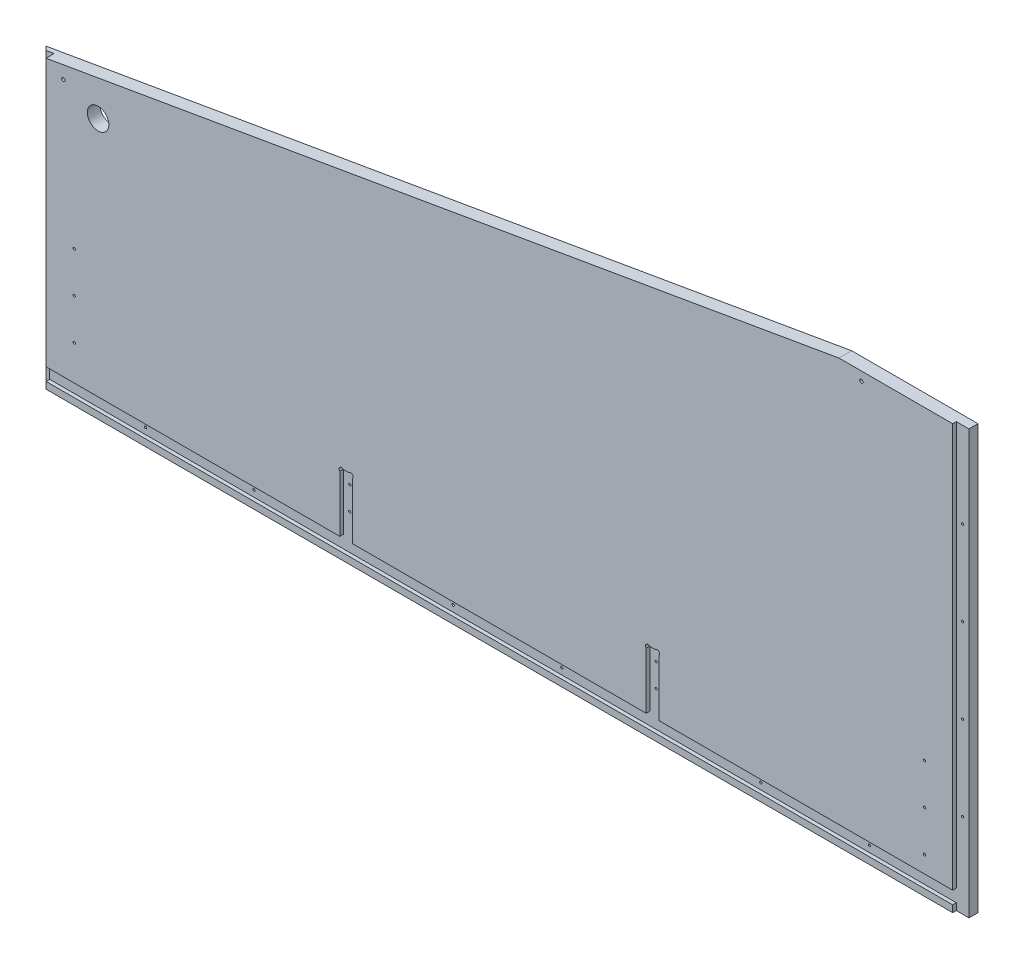
SolidWorks part; units mm, degrees
material "Maple"
ref_plane "Front Plane" through (0, 0, 0) normal (0, 0, 1) x (1, 0, 0)
ref_plane "Top Plane" through (0, 0, 0) normal (0, 1, 0) x (1, 0, 0)
ref_plane "Right Plane" through (0, 0, 0) normal (1, 0, 0) x (0, 0, -1)
sketch "Sketch1" plane through (0, 0, 0) normal (0, 0, 1) x (1, 0, 0)
  line L0 (8932.6508, -5243.5125) -> (10226.1458, -5243.5125)
  line L1 (9086.3208, -4722.0918) -> (10222.9708, -4853.7812)
  line L2 (8914.8708, -6342.0625) -> (10197.5708, -6342.0625)
  line L3 (8914.8708, -5808.6625) -> (10197.5708, -5808.6625)
  line L4 (8919.6333, -5253.0375) -> (10218.2083, -5253.0375)
  line L5 (9134.2633, -4656.1375) -> (9134.2633, -4638.3575)
  line L6 (9091.0833, -4638.3575) -> (9134.2633, -4638.3575)
  line L7 (9091.0833, -4567.2375) -> (9091.0833, -4638.3575)
  line L8 (9134.2633, -4656.1375) -> (9581.3033, -4656.1375)
  line L9 (9091.0833, -4567.2375) -> (9624.4833, -4567.2375)
  line L10 (9581.3033, -4656.1375) -> (9581.3033, -4638.3575)
  line L11 (9581.3033, -4638.3575) -> (9624.4833, -4638.3575)
  line L12 (9624.4833, -4567.2375) -> (9624.4833, -4638.3575)
  line L13 (8932.6508, -5225.7325) -> (9344.9775, -5225.7325)
  line L14 (8932.6508, -5256.2125) -> (8932.6508, -5243.5125)
  line L15 (8911.6958, -5256.2125) -> (8932.6508, -5256.2125)
  line L16 (8914.8708, -4722.0918) -> (9086.3208, -4722.0918)
  line L17 (8911.6958, -4715.5913) -> (8932.6508, -4715.5913)
  line L18 (8914.8708, -6342.0625) -> (8914.8708, -5808.6625)
  line L19 (12082.9917, -4722.0918) -> (10946.3417, -4853.7812)
  line L20 (12236.6617, -5243.5125) -> (10943.1667, -5243.5125)
  line L21 (10951.1042, -5253.0375) -> (12249.6792, -5253.0375)
  line L22 (10838.3917, -5656.2625) -> (11308.2917, -5656.2625)
  line L23 (10838.3917, -5719.7625) -> (11308.2917, -5719.7625)
  line L24 (10838.3917, -5742.5368) -> (11308.2917, -5742.5368)
  line L25 (10806.6417, -6342.0625) -> (11340.0417, -6342.0625)
  line L26 (10803.4667, -6335.7125) -> (11343.2167, -6335.7125)
  line L27 (10803.4667, -6317.9325) -> (11343.2167, -6317.9325)
  line L28 (10943.1667, -5225.7325) -> (11376.4483, -5225.7325)
  line L29 (11506.7292, -4754.5625) -> (10806.6417, -4827.5875)
  line L30 (11506.7292, -4567.2375) -> (11506.7292, -4754.5625)
  line L31 (10806.6417, -4567.2375) -> (10806.6417, -4827.5875)
  line L32 (10806.6417, -4567.2375) -> (11506.7292, -4567.2375)
  line L33 (10235.6708, -6329.3625) -> (10245.1958, -6329.3625)
  line L34 (10245.1958, -6329.3625) -> (10254.7208, -6278.5625)
  line L35 (10302.3458, -6329.3625) -> (10311.8708, -6278.5625)
  line L36 (10302.3458, -6329.3625) -> (10292.8208, -6329.3625)
  line L37 (10245.1958, -5821.3625) -> (10254.7208, -5872.1625)
  line L38 (10235.6708, -5821.3625) -> (10245.1958, -5821.3625)
  line L39 (10292.8208, -5821.3625) -> (10302.3458, -5821.3625)
  line L40 (10302.3458, -5821.3625) -> (10311.8708, -5872.1625)
  line L41 (10235.6708, -5821.3625) -> (10235.6708, -6329.3625)
  line L42 (10254.7208, -5872.1625) -> (10254.7208, -6278.5625)
  line L43 (10311.8708, -5872.1625) -> (10311.8708, -6278.5625)
  line L44 (10292.8208, -5821.3625) -> (10292.8208, -6329.3625)
  line L45 (8932.6508, -5225.7325) -> (8932.6508, -4715.5913)
  line L46 (8911.6958, -4715.5913) -> (8911.6958, -5256.2125)
  line L47 (8914.8708, -5248.275) -> (8914.8708, -4722.0918)
  line L48 (8919.6333, -5253.0375) -> (8914.8708, -5248.275)
  line L49 (8914.8708, -5145.0875) -> (8937.426, -5145.0875)
  line L50 (8914.8708, -5202.2375) -> (8937.426, -5202.2375)
  line L51 (10838.3917, -5656.2625) -> (10838.3917, -5719.7625)
  line L52 (10832.0417, -5736.1868) -> (10856.1717, -5736.1868)
  line L53 (10806.6417, -6342.0625) -> (10806.6417, -5818.7368)
  line L54 (10832.0417, -5649.9125) -> (10856.1717, -5649.9125)
  line L55 (10832.0417, -5726.1125) -> (10856.1717, -5726.1125)
  line L56 (10806.6417, -5818.7368) -> (10833.9015, -5818.7368)
  line L57 (10832.0417, -5806.0442) -> (10851.6815, -5806.0442)
  line L58 (10856.1717, -5801.5541) -> (10856.1717, -5736.1868)
  line L59 (10838.3917, -5814.2467) -> (10838.3917, -5742.5368)
  line L60 (10832.0417, -5806.0442) -> (10832.0417, -5736.1868)
  line L61 (10803.4667, -6317.9325) -> (10803.4667, -6335.7125)
  line L62 (10197.5708, -5808.6625) -> (10197.5708, -6342.0625)
  line L63 (9762.3842, -6348.4125) -> (9762.3842, -5802.3125)
  line L64 (9780.1642, -6348.4125) -> (9762.3842, -6348.4125)
  line L65 (9780.1642, -5802.3125) -> (9780.1642, -6348.4125)
  line L66 (9762.3842, -5802.3125) -> (9780.1642, -5802.3125)
  line L67 (9332.2775, -6348.4125) -> (9332.2775, -5802.3125)
  line L68 (9332.2775, -6348.4125) -> (9350.0575, -6348.4125)
  line L69 (9350.0575, -5802.3125) -> (9350.0575, -6348.4125)
  line L70 (9332.2775, -5802.3125) -> (9350.0575, -5802.3125)
  line L71 (9993.8374, -6061.075) -> (9993.8374, -6045.2418)
  line L72 (9998.5999, -6065.8375) -> (10014.4331, -6065.8375)
  line L73 (9998.5999, -6084.8875) -> (10014.4331, -6084.8875)
  line L74 (9993.8374, -6105.4832) -> (9993.8374, -6089.65)
  line L75 (9974.7874, -6105.4832) -> (9974.7874, -6089.65)
  line L76 (9954.1917, -6084.8875) -> (9970.0249, -6084.8875)
  line L77 (9974.7874, -6061.075) -> (9974.7874, -6045.2418)
  line L78 (9954.1917, -6065.8375) -> (9970.0249, -6065.8375)
  line L79 (10793.9417, -6237.2875) -> (10816.4969, -6237.2875)
  line L80 (10793.9417, -6294.4375) -> (10816.4969, -6294.4375)
  line L81 (10856.1717, -5649.9125) -> (10856.1717, -5726.1125)
  line L82 (10832.0417, -5726.1125) -> (10832.0417, -5649.9125)
  line L83 (10226.1458, -5225.7325) -> (10226.1458, -5243.5125)
  line L84 (10205.1908, -5257.8) -> (10205.1908, -4844.2499)
  line L85 (10230.9083, -4844.2499) -> (10230.9083, -5257.8)
  line L86 (10205.1908, -5257.8) -> (10230.9083, -5257.8)
  line L87 (10205.1908, -4844.2499) -> (10230.9083, -4844.2499)
  line L88 (10946.3417, -5176.8375) -> (10968.8969, -5176.8375)
  line L89 (9349.4676, -5141.9125) -> (9358.2674, -5141.9125)
  line L90 (10946.3417, -5119.6875) -> (10968.8969, -5119.6875)
  line L91 (9929.011, -4660.9635) -> (10066.0807, -4660.9635)
  line L92 (9929.011, -4678.7435) -> (10066.0807, -4678.7435)
  line L93 (10943.1667, -5225.7325) -> (10943.1667, -5243.5125)
  line L94 (10946.3417, -5248.275) -> (10951.1042, -5253.0375)
  line L95 (10946.3417, -5257.8063) -> (10946.3417, -4849.0188)
  line L96 (10964.1217, -5257.8) -> (10964.1217, -4844.2499)
  line L97 (10938.4042, -4844.2499) -> (10938.4042, -5257.8)
  line L98 (10938.4042, -5257.8) -> (10964.1217, -5257.8)
  line L99 (10964.1217, -4844.2499) -> (10938.4042, -4844.2499)
  line L100 (10344.8908, -4560.8875) -> (10369.0208, -4560.8875)
  line L101 (10344.8908, -4560.8875) -> (10369.0208, -4560.8875)
  line L102 (10800.2917, -4560.8875) -> (10824.4217, -4560.8875)
  line L103 (10200.4156, -5119.6875) -> (10222.9708, -5119.6875)
  line L104 (10200.4156, -5176.8375) -> (10222.9708, -5176.8375)
  line L105 (9344.9775, -5146.4026) -> (9344.9775, -5225.7325)
  line L106 (10344.8908, -4560.8875) -> (10344.8908, -4833.9375)
  line L107 (9792.8642, -5225.7325) -> (9792.8642, -5146.4026)
  line L108 (9362.7575, -5225.7325) -> (9775.0842, -5225.7325)
  line L109 (9680.3633, -4761.8396) -> (9680.3633, -4559.9604)
  line L110 (9656.2333, -4559.9604) -> (9680.3633, -4559.9604)
  line L111 (9656.2333, -4761.8396) -> (9680.3633, -4761.8396)
  line L112 (9656.2333, -4761.8396) -> (9656.2333, -4559.9604)
  line L113 (9779.5743, -5141.9125) -> (9788.374, -5141.9125)
  line L114 (10070.5708, -4665.4536) -> (10070.5708, -4674.2534)
  line L115 (9924.5208, -4674.2534) -> (9924.5208, -4665.4536)
  line L116 (12127.4417, -6188.3925) -> (12205.5015, -6188.3925)
  line L117 (12209.9917, -6170.6125) -> (12209.9917, -6183.9024)
  line L118 (9792.8642, -5225.7325) -> (10226.1458, -5225.7325)
  line L119 (9662.5833, -4754.5625) -> (10362.6708, -4827.5875)
  line L120 (9662.5833, -4567.2375) -> (9662.5833, -4754.5625)
  line L121 (10362.6708, -4567.2375) -> (10362.6708, -4827.5875)
  line L122 (9662.5833, -4567.2375) -> (10362.6708, -4567.2375)
  line L123 (10824.4217, -4833.9375) -> (10800.2917, -4833.9375)
  line L124 (10800.2917, -4833.9375) -> (10800.2917, -4560.8875)
  line L125 (10824.4217, -4560.8875) -> (10824.4217, -4833.9375)
  line L126 (10344.8908, -4833.9375) -> (10369.0208, -4833.9375)
  line L127 (10369.0208, -4833.9375) -> (10369.0208, -4560.8875)
  line L128 (10222.9708, -5248.275) -> (10218.2083, -5253.0375)
  line L129 (10222.9708, -5257.8063) -> (10222.9708, -4849.0188)
  line L130 (11734.6544, -5701.375) -> (11739.2301, -5701.375)
  line L131 (9362.7575, -5225.7325) -> (9362.7575, -5146.4026)
  line L132 (9775.0842, -5146.4026) -> (9775.0842, -5225.7325)
  line L133 (11761.3864, -5701.375) -> (11756.8282, -5701.375)
  line L134 (11734.6544, -5693.755) -> (11739.2301, -5693.755)
  line L135 (11761.4039, -5693.755) -> (11756.8282, -5693.755)
  line L136 (11734.6544, -5701.375) -> (11739.2301, -5701.375)
  line L137 (11744.3462, -5721.3024) -> (11744.3462, -5706.4179)
  line L138 (11751.7122, -5721.3024) -> (11751.7122, -5706.4179)
  line L139 (11740.0917, -6170.6125) -> (11740.0917, -6183.9024)
  line L140 (11689.2917, -6188.3925) -> (11822.6417, -6188.3925)
  line L141 (11689.2917, -6348.4093) -> (11689.2917, -6164.2657)
  line L142 (11689.2917, -6164.2657) -> (11746.4417, -6164.2657)
  line L143 (11746.4417, -6164.2657) -> (11746.4417, -6188.3925)
  line L144 (11689.2917, -6164.2657) -> (11746.4417, -6164.2657)
  line L145 (11340.0417, -5818.7368) -> (11340.0417, -6342.0625)
  line L146 (11290.5117, -5726.1125) -> (11314.6417, -5726.1125)
  line L147 (11290.5117, -5649.9125) -> (11290.5117, -5726.1125)
  line L148 (11340.0417, -5818.7368) -> (11312.7818, -5818.7368)
  line L149 (11314.6417, -5806.0442) -> (11295.0018, -5806.0442)
  line L150 (11290.5117, -5801.5541) -> (11290.5117, -5736.1868)
  line L151 (11308.2917, -5814.2467) -> (11308.2917, -5742.5368)
  line L152 (11314.6417, -5806.0442) -> (11314.6417, -5736.1868)
  line L153 (11290.5117, -5736.1868) -> (11314.6417, -5736.1868)
  line L154 (11848.0417, -6267.1325) -> (11962.3417, -6267.1325)
  line L155 (11962.3417, -6267.1325) -> (11962.3417, -6203.6325)
  line L156 (11343.2167, -6317.9325) -> (11343.2167, -6335.7125)
  line L157 (11365.4417, -5656.2625) -> (11365.4417, -5719.7625)
  line L158 (11365.4417, -5656.2625) -> (11479.7417, -5656.2625)
  line L159 (11778.1917, -6071.3937) -> (11802.3217, -6071.3937)
  line L160 (11314.6417, -5726.1125) -> (11314.6417, -5649.9125)
  line L161 (11314.6417, -5649.9125) -> (11290.5117, -5649.9125)
  line L162 (11308.2917, -5719.7625) -> (11308.2917, -5656.2625)
  line L163 (11689.2917, -6348.4093) -> (11713.4217, -6348.4093)
  line L164 (12203.6417, -6164.2657) -> (12260.7917, -6164.2657)
  line L165 (11713.4217, -6348.4093) -> (11713.4217, -6164.2657)
  line L166 (11695.6417, -6342.0625) -> (11695.6417, -6170.6125)
  line L167 (11695.6417, -6048.5337) -> (11699.4517, -6052.3437)
  line L168 (11822.6417, -6292.5325) -> (11822.6417, -6188.3925)
  line L169 (11695.6417, -6342.0625) -> (11695.6417, -6170.6125)
  line L170 (11848.0417, -6203.6325) -> (11962.3417, -6203.6325)
  line L171 (11848.0417, -6203.6325) -> (11848.0417, -6267.1325)
  line L172 (11987.7417, -6267.1325) -> (11987.7417, -6203.6325)
  line L173 (11784.5417, -6077.7437) -> (11784.5417, -6141.2438)
  line L174 (11517.8417, -5656.2625) -> (11632.1417, -5656.2625)
  line L175 (11632.1417, -5656.2625) -> (11632.1417, -5719.7625)
  line L176 (11632.1417, -5719.7625) -> (11517.8417, -5719.7625)
  line L177 (11517.8417, -5719.7625) -> (11517.8417, -5656.2625)
  line L178 (11692.4667, -6028.2137) -> (11692.4667, -6045.9937)
  line L179 (11695.6417, -5979.3188) -> (11718.1969, -5979.3188)
  line L180 (11695.6417, -5922.1687) -> (11718.1969, -5922.1687)
  line L181 (11821.0415, -5722.9375) -> (11821.0415, -5943.6)
  line L182 (11687.7042, -5651.5) -> (11701.9917, -5651.5)
  line L183 (11687.7042, -5651.5) -> (11687.7042, -6055.5251)
  line L184 (11687.7042, -6055.5251) -> (11701.9917, -6055.5251)
  line L185 (11701.9917, -6055.5251) -> (11701.9917, -5651.5)
  line L186 (11695.6417, -6055.2013) -> (11695.6417, -5649.595)
  line L187 (11695.6417, -5656.2625) -> (11695.6417, -6048.5337)
  line L188 (11695.6417, -6170.6125) -> (11740.0917, -6170.6125)
  line L189 (12203.6417, -6164.2657) -> (12203.6417, -6188.3925)
  line L190 (12254.4417, -6342.0625) -> (12254.4417, -6170.6125)
  line L191 (12129.0419, -5943.6) -> (12129.0419, -5722.9375)
  line L192 (12254.4417, -6048.5337) -> (12250.6317, -6052.3437)
  line L193 (12257.6167, -6045.9937) -> (12257.6167, -6028.2137)
  line L194 (12248.0917, -5651.5) -> (12262.3792, -5651.5)
  line L195 (12262.3792, -5651.5) -> (12262.3792, -6055.5251)
  line L196 (12262.3792, -6055.5251) -> (12248.0917, -6055.5251)
  line L197 (12248.0917, -6055.5251) -> (12248.0917, -5651.5)
  line L198 (12254.4417, -6141.2438) -> (12254.4417, -6077.7437)
  line L199 (12236.6617, -6164.2657) -> (12260.7917, -6164.2657)
  line L200 (12102.0417, -6267.1325) -> (11987.7417, -6267.1325)
  line L201 (11330.1865, -6237.2875) -> (11352.7417, -6237.2875)
  line L202 (11330.1865, -6294.4375) -> (11352.7417, -6294.4375)
  line L203 (11474.6617, -5851.8425) -> (11492.4417, -5851.8425)
  line L204 (11474.6617, -5808.6625) -> (11474.6617, -5851.8425)
  line L205 (11403.5417, -5808.6625) -> (11474.6617, -5808.6625)
  line L206 (11492.4417, -5851.8425) -> (11492.4417, -6298.8825)
  line L207 (11403.5417, -6342.0625) -> (11403.5417, -5808.6625)
  line L208 (11474.6617, -6298.8825) -> (11492.4417, -6298.8825)
  line L209 (11474.6617, -6342.0625) -> (11474.6617, -6298.8825)
  line L210 (11403.5417, -6342.0625) -> (11474.6617, -6342.0625)
  line L211 (11619.4417, -5851.8425) -> (11601.6617, -5851.8425)
  line L212 (11601.6617, -5808.6625) -> (11601.6617, -5851.8425)
  line L213 (11530.5417, -5808.6625) -> (11601.6617, -5808.6625)
  line L214 (11619.4417, -5851.8425) -> (11619.4417, -6298.8825)
  line L215 (11530.5417, -6342.0625) -> (11530.5417, -5808.6625)
  line L216 (11619.4417, -6298.8825) -> (11601.6617, -6298.8825)
  line L217 (11601.6617, -6342.0625) -> (11601.6617, -6298.8825)
  line L218 (11530.5417, -6342.0625) -> (11601.6617, -6342.0625)
  line L219 (11479.7417, -5719.7625) -> (11479.7417, -5656.2625)
  line L220 (11365.4417, -5719.7625) -> (11479.7417, -5719.7625)
  line L221 (11778.1917, -6147.5937) -> (11802.3217, -6147.5937)
  line L222 (11802.3217, -6071.3937) -> (11802.3217, -6147.5937)
  line L223 (11778.1917, -6147.5937) -> (11778.1917, -6071.3937)
  line L224 (12254.4417, -5922.1687) -> (12231.8865, -5922.1687)
  line L225 (12254.4417, -5979.3188) -> (12231.8865, -5979.3188)
  line L226 (12254.4417, -6055.2013) -> (12254.4417, -5649.595)
  line L227 (12254.4417, -6048.5337) -> (12254.4417, -5656.2625)
  line L228 (11841.6917, -5702.2873) -> (12108.3917, -5702.2873)
  line L229 (11822.6417, -6292.5325) -> (12127.4417, -6292.5325)
  line L230 (12127.4417, -6292.5325) -> (12127.4417, -6188.3925)
  line L231 (12254.4417, -6170.6125) -> (12209.9917, -6170.6125)
  line L232 (11695.6417, -6342.0625) -> (12254.4417, -6342.0625)
  line L233 (12236.6617, -6348.4093) -> (12260.7917, -6348.4093)
  line L234 (12260.7917, -6348.4093) -> (12260.7917, -6164.2657)
  line L235 (12236.6617, -6348.4093) -> (12236.6617, -6164.2657)
  line L236 (12102.0417, -6203.6325) -> (12102.0417, -6267.1325)
  line L237 (11987.7417, -6203.6325) -> (12102.0417, -6203.6325)
  line L238 (12236.6617, -6147.5937) -> (12236.6617, -6071.3937)
  line L239 (12203.6417, -6188.3925) -> (12260.7917, -6188.3925)
  line L240 (11098.7417, -4665.4536) -> (11098.7417, -4674.2534)
  line L241 (11394.2283, -5146.4026) -> (11394.2283, -5225.7325)
  line L242 (11376.4483, -5225.7325) -> (11376.4483, -5146.4026)
  line L243 (11394.2283, -5225.7325) -> (11806.555, -5225.7325)
  line L244 (11841.6917, -5964.2502) -> (12108.3917, -5964.2502)
  line L245 (12236.6617, -6147.5937) -> (12260.7917, -6147.5937)
  line L246 (12236.6617, -5256.2125) -> (12236.6617, -5243.5125)
  line L247 (12260.7917, -6147.5937) -> (12260.7917, -6071.3937)
  line L248 (12260.7917, -6071.3937) -> (12236.6617, -6071.3937)
  line L249 (12254.4417, -6077.7437) -> (11784.5417, -6077.7437)
  line L250 (11784.5417, -6141.2438) -> (12254.4417, -6141.2438)
  line L252 (12254.4417, -5656.2625) -> (11695.6417, -5656.2625)
  line L253 (11699.4517, -6052.3437) -> (12250.6317, -6052.3437)
  line L254 (11692.4667, -6045.9937) -> (12257.6167, -6045.9937)
  line L255 (11692.4667, -6028.2137) -> (12257.6167, -6028.2137)
  line L256 (11824.335, -5146.4026) -> (11824.335, -5225.7325)
  line L257 (11811.0451, -5141.9125) -> (11819.8449, -5141.9125)
  line L258 (11244.7917, -4674.2534) -> (11244.7917, -4665.4536)
  line L259 (11806.555, -5225.7325) -> (11806.555, -5146.4026)
  line L260 (11488.9492, -4761.8396) -> (11488.9492, -4559.9604)
  line L261 (11488.9492, -4559.9604) -> (11513.0792, -4559.9604)
  line L262 (11488.9492, -4761.8396) -> (11513.0792, -4761.8396)
  line L263 (11513.0792, -4761.8396) -> (11513.0792, -4559.9604)
  line L264 (11240.3015, -4660.9635) -> (11103.2318, -4660.9635)
  line L265 (11103.2318, -4678.7435) -> (11240.3015, -4678.7435)
  line L266 (12236.6617, -5225.7325) -> (12236.6617, -4715.5913)
  line L267 (12257.6167, -4715.5913) -> (12257.6167, -5256.2125)
  line L268 (12254.4417, -5248.275) -> (12254.4417, -4722.0918)
  line L269 (12236.6617, -5225.7325) -> (11824.335, -5225.7325)
  line L270 (12035.0492, -4656.1375) -> (12035.0492, -4638.3575)
  line L271 (12078.2292, -4638.3575) -> (12035.0492, -4638.3575)
  line L272 (12078.2292, -4567.2375) -> (12078.2292, -4638.3575)
  line L273 (12035.0492, -4656.1375) -> (11588.0092, -4656.1375)
  line L274 (11544.8292, -4567.2375) -> (12078.2292, -4567.2375)
  line L275 (11588.0092, -4656.1375) -> (11588.0092, -4638.3575)
  line L276 (11544.8292, -4638.3575) -> (11588.0092, -4638.3575)
  line L277 (11544.8292, -4567.2375) -> (11544.8292, -4638.3575)
  line L278 (12249.6792, -5253.0375) -> (12254.4417, -5248.275)
  line L280 (12257.6167, -5256.2125) -> (12236.6617, -5256.2125)
  line L281 (12231.8865, -5145.0875) -> (12254.4417, -5145.0875)
  line L282 (12231.8865, -5202.2375) -> (12254.4417, -5202.2375)
  line L283 (12236.6617, -4715.5913) -> (12257.6167, -4715.5913)
  line L284 (12082.9917, -4722.0918) -> (12254.4417, -4722.0918)
  line L285 (11380.9385, -5141.9125) -> (11389.7382, -5141.9125)
  circle A0 centre (8923.7608, -4778.9042) radius 1.5875
  circle A1 centre (9062.6598, -4736.3765) radius 2.3685
  circle A2 centre (9051.3958, -6281.7375) radius 22.225
  circle A3 centre (9083.1458, -6249.9875) radius 1.5875
  circle A4 centre (9083.1458, -6313.4875) radius 1.5875
  circle A5 centre (9019.6458, -6249.9875) radius 1.5875
  circle A6 centre (9019.6458, -6313.4875) radius 1.5875
  circle A7 centre (8972.3383, -5202.2375) radius 1.5875
  circle A8 centre (8923.7608, -5015.9708) radius 1.5875
  circle A9 centre (8923.7608, -5134.5042) radius 1.5875
  circle A10 centre (9054.5708, -5234.6225) radius 1.5875
  circle A11 centre (8923.7608, -4897.4375) radius 1.5875
  circle A12 centre (8972.3383, -5087.9375) radius 1.5875
  circle A13 centre (8972.3383, -5145.0875) radius 1.5875
  circle A14 centre (10847.2817, -5668.9625) radius 1.5875
  circle A15 centre (10847.2817, -5707.0625) radius 1.5875
  circle A16 centre (10847.2817, -5755.2368) radius 1.5875
  circle A17 centre (10851.4092, -6237.2875) radius 1.5875
  circle A18 centre (10851.4092, -6294.4375) radius 1.5875
  circle A19 centre (10847.2817, -5793.3442) radius 1.5875
  arc A20 (10833.9015, -5818.7368) -> (10838.3917, -5814.2467) centre (10836.1466, -5816.4918) ccw
  arc A21 (10851.6815, -5806.0442) -> (10856.1717, -5801.5541) centre (10853.9266, -5803.7992) ccw
  circle A22 centre (10882.8417, -6040.4375) radius 1.5875
  circle A23 centre (10882.8417, -6218.2375) radius 1.5875
  circle A24 centre (10882.8417, -5862.6375) radius 1.5875
  circle A25 centre (10908.2417, -6326.8225) radius 1.5875
  circle A26 centre (10908.2417, -6326.8225) radius 1.5875
  circle A27 centre (10851.4092, -6180.1375) radius 1.5875
  circle A28 centre (10815.5317, -4783.4231) radius 1.5875
  circle A29 centre (10815.5317, -4696.9488) radius 1.5875
  circle A30 centre (10815.5317, -4610.4746) radius 1.5875
  circle A31 centre (10979.1323, -4867.0082) radius 2.3685
  circle A32 centre (10190.1802, -4867.0082) radius 2.3685
  circle A33 centre (10955.2317, -4929.9812) radius 1.5875
  circle A34 centre (10955.2317, -5031.5812) radius 1.5875
  circle A35 centre (10214.0808, -4929.9812) radius 1.5875
  circle A36 centre (10214.0808, -5031.5812) radius 1.5875
  circle A37 centre (9341.1675, -6265.8625) radius 1.5875
  circle A38 centre (9771.2742, -5884.8625) radius 1.5875
  circle A39 centre (9771.2742, -6138.8625) radius 1.5875
  circle A40 centre (9771.2742, -6011.8625) radius 1.5875
  arc A41 (10036.2287, -6113.8083) -> (10051.3426, -6111.6033) centre (10042.9639, -6107.0732) ccw
  arc A42 (10051.3426, -6111.6033) -> (10051.3426, -6039.1217) centre (9984.3124, -6075.3625) ccw
  arc A43 (10051.3426, -6039.1217) -> (10036.2287, -6036.9167) centre (10042.9639, -6043.6518) ccw
  arc A44 (10034.5851, -6102.5431) -> (10034.5851, -6048.1819) centre (9984.3124, -6075.3625) ccw
  arc A45 (10034.5851, -6102.5431) -> (10036.2287, -6113.8083) centre (10042.9639, -6107.0732) ccw
  arc A46 (10036.2287, -6036.9167) -> (10034.5851, -6048.1819) centre (10042.9639, -6043.6518) ccw
  arc A47 (9945.8666, -6127.2787) -> (9948.0717, -6142.3927) centre (9952.6018, -6134.0139) ccw
  arc A48 (9948.0717, -6142.3927) -> (10020.5532, -6142.3927) centre (9984.3124, -6075.3625) ccw
  arc A49 (10020.5532, -6142.3927) -> (10022.7583, -6127.2787) centre (10016.0231, -6134.0139) ccw
  arc A50 (9957.1319, -6125.6352) -> (10011.493, -6125.6352) centre (9984.3124, -6075.3625) ccw
  arc A51 (9957.1319, -6125.6352) -> (9945.8666, -6127.2787) centre (9952.6018, -6134.0139) ccw
  arc A52 (10022.7583, -6127.2787) -> (10011.493, -6125.6352) centre (10016.0231, -6134.0139) ccw
  arc A53 (9932.3962, -6036.9167) -> (9917.2822, -6039.1217) centre (9925.661, -6043.6518) ccw
  arc A54 (9917.2822, -6039.1217) -> (9917.2822, -6111.6033) centre (9984.3124, -6075.3625) ccw
  arc A55 (9917.2822, -6111.6033) -> (9932.3962, -6113.8083) centre (9925.661, -6107.0732) ccw
  arc A56 (9934.0398, -6048.1819) -> (9934.0398, -6102.5431) centre (9984.3124, -6075.3625) ccw
  arc A57 (9934.0398, -6048.1819) -> (9932.3962, -6036.9167) centre (9925.661, -6043.6518) ccw
  arc A58 (9932.3962, -6113.8083) -> (9934.0398, -6102.5431) centre (9925.661, -6107.0732) ccw
  arc A59 (9945.8666, -6023.4463) -> (9957.1319, -6025.0898) centre (9952.6018, -6016.7111) ccw
  arc A60 (10011.493, -6025.0898) -> (10022.7583, -6023.4463) centre (10016.0231, -6016.7111) ccw
  arc A61 (10011.493, -6025.0898) -> (9957.1319, -6025.0898) centre (9984.3124, -6075.3625) ccw
  arc A62 (9948.0717, -6008.3323) -> (9945.8666, -6023.4463) centre (9952.6018, -6016.7111) ccw
  arc A63 (10020.5532, -6008.3323) -> (9948.0717, -6008.3323) centre (9984.3124, -6075.3625) ccw
  arc A64 (10022.7583, -6023.4463) -> (10020.5532, -6008.3323) centre (10016.0231, -6016.7111) ccw
  arc A65 (10005.0943, -6187.7574) -> (10096.7073, -6096.1443) centre (9984.3124, -6075.3625) ccw
  arc A66 (9993.8374, -6178.3911) -> (10005.0943, -6187.7574) centre (10003.3624, -6178.3911) ccw
  arc A67 (10001.6306, -6169.0249) -> (10077.9748, -6092.6807) centre (9984.3124, -6075.3625) ccw
  arc A68 (10087.3411, -6084.8875) -> (10077.9748, -6092.6807) centre (10087.3411, -6094.4125) ccw
  arc A69 (10001.6306, -6169.0249) -> (9993.8374, -6178.3911) centre (10003.3624, -6178.3911) ccw
  arc A70 (9963.5306, -6187.7574) -> (9974.7874, -6178.3911) centre (9965.2624, -6178.3911) ccw
  arc A71 (9871.9176, -6096.1443) -> (9963.5306, -6187.7574) centre (9984.3124, -6075.3625) ccw
  arc A72 (9881.2838, -6084.8875) -> (9871.9176, -6096.1443) centre (9881.2838, -6094.4125) ccw
  arc A73 (9890.65, -6092.6807) -> (9966.9943, -6169.0249) centre (9984.3124, -6075.3625) ccw
  arc A74 (9974.7874, -6178.3911) -> (9966.9943, -6169.0249) centre (9965.2624, -6178.3911) ccw
  arc A75 (9890.65, -6092.6807) -> (9881.2838, -6084.8875) centre (9881.2838, -6094.4125) ccw
  arc A76 (9871.9176, -6054.5807) -> (9881.2838, -6065.8375) centre (9881.2838, -6056.3125) ccw
  arc A77 (9963.5306, -5962.9676) -> (9871.9176, -6054.5807) centre (9984.3124, -6075.3625) ccw
  arc A78 (9974.7874, -5972.3339) -> (9963.5306, -5962.9676) centre (9965.2624, -5972.3339) ccw
  arc A79 (9966.9943, -5981.7001) -> (9890.65, -6058.0443) centre (9984.3124, -6075.3625) ccw
  arc A80 (9881.2838, -6065.8375) -> (9890.65, -6058.0443) centre (9881.2838, -6056.3125) ccw
  arc A81 (9966.9943, -5981.7001) -> (9974.7874, -5972.3339) centre (9965.2624, -5972.3339) ccw
  arc A82 (10077.9748, -6058.0443) -> (10087.3411, -6065.8375) centre (10087.3411, -6056.3125) ccw
  arc A83 (9993.8374, -5972.3339) -> (10001.6306, -5981.7001) centre (10003.3624, -5972.3339) ccw
  arc A84 (10077.9748, -6058.0443) -> (10001.6306, -5981.7001) centre (9984.3124, -6075.3625) ccw
  arc A85 (10087.3411, -6065.8375) -> (10096.7073, -6054.5807) centre (10087.3411, -6056.3125) ccw
  arc A86 (10096.7073, -6054.5807) -> (10005.0943, -5962.9676) centre (9984.3124, -6075.3625) ccw
  arc A87 (10005.0943, -5962.9676) -> (9993.8374, -5972.3339) centre (10003.3624, -5972.3339) ccw
  arc A88 (10014.4331, -6065.8375) -> (10018.7361, -6059.0339) centre (10014.4331, -6061.075) ccw
  arc A89 (10018.7361, -6059.0339) -> (10000.641, -6040.9388) centre (9984.3124, -6075.3625) ccw
  arc A90 (10000.641, -6040.9388) -> (9993.8374, -6045.2418) centre (9998.5999, -6045.2418) ccw
  arc A91 (9993.8374, -6061.075) -> (9998.5999, -6065.8375) centre (9998.5999, -6061.075) ccw
  arc A92 (9993.8374, -6105.4832) -> (10000.641, -6109.7862) centre (9998.5999, -6105.4832) ccw
  arc A93 (10000.641, -6109.7862) -> (10018.7361, -6091.6911) centre (9984.3124, -6075.3625) ccw
  arc A94 (10018.7361, -6091.6911) -> (10014.4331, -6084.8875) centre (10014.4331, -6089.65) ccw
  arc A95 (9998.5999, -6084.8875) -> (9993.8374, -6089.65) centre (9998.5999, -6089.65) ccw
  arc A96 (9954.1917, -6084.8875) -> (9949.8888, -6091.6911) centre (9954.1917, -6089.65) ccw
  arc A97 (9949.8888, -6091.6911) -> (9967.9839, -6109.7862) centre (9984.3124, -6075.3625) ccw
  arc A98 (9967.9839, -6109.7862) -> (9974.7874, -6105.4832) centre (9970.0249, -6105.4832) ccw
  arc A99 (9974.7874, -6089.65) -> (9970.0249, -6084.8875) centre (9970.0249, -6089.65) ccw
  arc A100 (9970.0249, -6065.8375) -> (9974.7874, -6061.075) centre (9970.0249, -6061.075) ccw
  arc A101 (9949.8888, -6059.0339) -> (9954.1917, -6065.8375) centre (9954.1917, -6061.075) ccw
  arc A102 (9967.9839, -6040.9388) -> (9949.8888, -6059.0339) centre (9984.3124, -6075.3625) ccw
  arc A103 (9974.7874, -6045.2418) -> (9967.9839, -6040.9388) centre (9970.0249, -6045.2418) ccw
  arc A104 (10096.7073, -6096.1443) -> (10087.3411, -6084.8875) centre (10087.3411, -6094.4125) ccw
  circle A105 centre (9771.2742, -6265.8625) radius 1.5875
  circle A106 centre (9341.1675, -5884.8625) radius 1.5875
  circle A107 centre (9341.1675, -6138.8625) radius 1.5875
  circle A108 centre (9341.1675, -6011.8625) radius 1.5875
  circle A109 centre (11037.2315, -4887.5494) radius 15.0812
  arc A110 (9349.4676, -5141.9125) -> (9344.9775, -5146.4026) centre (9347.2226, -5144.1576) ccw
  arc A111 (9362.7575, -5146.4026) -> (9358.2674, -5141.9125) centre (9360.5124, -5144.1576) ccw
  circle A112 centre (9946.7458, -4669.8535) radius 1.5875
  arc A113 (9924.5208, -4674.2534) -> (9929.011, -4678.7435) centre (9926.7659, -4676.4984) ccw
  circle A114 centre (11003.8092, -5176.8375) radius 1.5875
  circle A115 centre (11003.8092, -5119.6875) radius 1.5875
  circle A116 centre (10353.7808, -4696.9488) radius 1.5875
  circle A117 centre (10353.7808, -4610.4746) radius 1.5875
  circle A118 centre (10353.7808, -4783.4231) radius 1.5875
  circle A119 centre (11003.8092, -5062.5375) radius 1.5875
  circle A120 centre (9353.8675, -5160.9625) radius 1.5875
  circle A121 centre (9638.7708, -5234.6225) radius 1.5875
  circle A122 centre (9671.4733, -4724.1144) radius 1.5875
  circle A123 centre (9671.4733, -4661.3637) radius 1.5875
  circle A124 centre (9671.4733, -4598.6129) radius 1.5875
  arc A125 (9792.8642, -5146.4026) -> (9788.374, -5141.9125) centre (9790.6191, -5144.1576) ccw
  arc A126 (9779.5743, -5141.9125) -> (9775.0842, -5146.4026) centre (9777.3292, -5144.1576) ccw
  circle A127 centre (10048.3458, -4669.8535) radius 1.5875
  arc A128 (10070.5708, -4665.4536) -> (10066.0807, -4660.9635) centre (10068.3258, -4663.2086) ccw
  arc A129 (10066.0807, -4678.7435) -> (10070.5708, -4674.2534) centre (10068.3258, -4676.4984) ccw
  circle A130 centre (9997.5458, -4669.8535) radius 1.5875
  arc A131 (9929.011, -4660.9635) -> (9924.5208, -4665.4536) centre (9926.7659, -4663.2086) ccw
  circle A132 centre (10132.081, -4887.5494) radius 15.0812
  circle A133 centre (10165.5033, -5176.8375) radius 1.5875
  circle A134 centre (10165.5033, -5119.6875) radius 1.5875
  circle A135 centre (9486.3708, -5234.6225) radius 1.5875
  circle A136 centre (10165.5033, -5062.5375) radius 1.5875
  circle A137 centre (9206.9708, -5234.6225) radius 1.5875
  circle A138 centre (10070.5708, -5234.6225) radius 1.5875
  circle A139 centre (9918.1708, -5234.6225) radius 1.5875
  circle A140 centre (9783.9742, -5160.9625) radius 1.5875
  circle A141 centre (9783.9742, -5193.9825) radius 1.5875
  circle A142 centre (9353.8675, -5193.9825) radius 1.5875
  circle A143 centre (11073.3417, -6326.8225) radius 1.5875
  circle A144 centre (11073.3417, -6326.8225) radius 1.5875
  circle A145 centre (11295.2742, -6180.1375) radius 1.5875
  circle A146 centre (11295.2742, -6294.4375) radius 1.5875
  circle A147 centre (11295.2742, -6237.2875) radius 1.5875
  circle A148 centre (11975.0417, -5692.775) radius 3.4925
  circle A149 centre (11263.8417, -5862.6375) radius 1.5875
  arc A150 (11739.2301, -5701.375) -> (11744.3462, -5706.4179) centre (11748.0292, -5697.565) ccw
  arc A151 (11751.7122, -5706.4179) -> (11756.8282, -5701.375) centre (11748.0292, -5697.565) ccw
  arc A152 (11744.3462, -5721.3024) -> (11751.7122, -5721.3024) centre (11748.0292, -5725.505) ccw
  arc A153 (11734.6544, -5693.755) -> (11724.9787, -5697.565) centre (11730.5667, -5697.565) ccw
  arc A154 (11756.8282, -5693.755) -> (11739.2301, -5693.755) centre (11748.0292, -5697.565) ccw
  arc A155 (11724.9787, -5697.565) -> (11734.6544, -5701.375) centre (11730.5667, -5697.565) ccw
  arc A156 (11761.3864, -5701.375) -> (11771.0797, -5697.565) centre (11765.4842, -5697.565) ccw
  arc A157 (11771.0797, -5697.565) -> (11761.4039, -5693.755) centre (11765.4917, -5697.565) ccw
  arc A158 (11740.0917, -6183.9024) -> (11744.5818, -6188.3925) centre (11742.3367, -6186.1474) ccw
  arc A159 (12205.5015, -6188.3925) -> (12209.9917, -6183.9024) centre (12207.7466, -6186.1474) ccw
  circle A160 centre (11299.4017, -5793.3442) radius 1.5875
  arc A161 (11308.2917, -5814.2467) -> (11312.7818, -5818.7368) centre (11310.5367, -5816.4918) ccw
  arc A162 (11290.5117, -5801.5541) -> (11295.0018, -5806.0442) centre (11292.7567, -5803.7992) ccw
  circle A163 centre (11704.5317, -6314.149) radius 1.5875
  circle A164 centre (11748.9817, -6208.7125) radius 1.5875
  circle A165 centre (11263.8417, -6218.2375) radius 1.5875
  circle A166 centre (11263.8417, -6040.4375) radius 1.5875
  circle A167 centre (11238.4417, -6326.8225) radius 1.5875
  circle A168 centre (11238.4417, -6326.8225) radius 1.5875
  circle A169 centre (11299.4017, -5668.9625) radius 1.5875
  circle A170 centre (11299.4017, -5707.0625) radius 1.5875
  circle A171 centre (11726.7567, -6179.5025) radius 1.5875
  circle A172 centre (11704.5317, -6199.3198) radius 1.5875
  circle A173 centre (11748.9817, -6272.2125) radius 1.5875
  circle A174 centre (11704.5317, -6256.7344) radius 1.5875
  circle A175 centre (11299.4017, -5755.2368) radius 1.5875
  circle A176 centre (11913.4467, -6301.4225) radius 1.5875
  circle A177 centre (11790.2567, -6301.4225) radius 1.5875
  circle A178 centre (11793.4317, -6128.5437) radius 1.5875
  circle A179 centre (11753.1092, -5865.0188) radius 1.5875
  circle A180 centre (11809.9417, -6037.1038) radius 1.5875
  circle A181 centre (11809.9417, -6037.1038) radius 1.5875
  circle A182 centre (11753.1092, -5922.1687) radius 1.5875
  circle A183 centre (11975.0417, -5973.7625) radius 3.4925
  circle A184 centre (11975.0417, -6037.1038) radius 1.5875
  circle A185 centre (11753.1092, -5979.3188) radius 1.5875
  circle A186 centre (11975.0417, -6037.1038) radius 1.5875
  arc A187 (11841.6917, -5702.2873) -> (11821.0415, -5722.9375) centre (11841.6917, -5722.9375) ccw
  circle A188 centre (11811.5292, -5833.2687) radius 3.4925
  arc A189 (11821.0415, -5943.6) -> (11841.6917, -5964.2502) centre (11841.6917, -5943.6) ccw
  circle A190 centre (12196.9742, -5865.0188) radius 1.5875
  arc A191 (12129.0419, -5722.9375) -> (12108.3917, -5702.2873) centre (12108.3917, -5722.9375) ccw
  circle A192 centre (12036.6367, -6301.4225) radius 1.5875
  circle A193 centre (12159.8267, -6301.4225) radius 1.5875
  circle A194 centre (12138.5542, -5833.2687) radius 3.4925
  circle A195 centre (12197.2917, -5761.0375) radius 15.0812
  circle A196 centre (11793.4317, -6090.4437) radius 1.5875
  circle A197 centre (12196.9742, -5922.1687) radius 1.5875
  arc A198 (12108.3917, -5964.2502) -> (12129.0419, -5943.6) centre (12108.3917, -5943.6) ccw
  circle A199 centre (12196.9742, -5979.3188) radius 1.5875
  circle A200 centre (12201.1017, -6272.2125) radius 1.5875
  circle A201 centre (12245.5517, -6314.149) radius 1.5875
  circle A202 centre (12245.5517, -6256.7344) radius 1.5875
  circle A203 centre (12201.1017, -6208.7125) radius 1.5875
  circle A204 centre (12223.3267, -6179.5025) radius 1.5875
  circle A205 centre (12245.5517, -6199.3198) radius 1.5875
  circle A206 centre (11171.7667, -4669.8535) radius 1.5875
  circle A207 centre (11222.5667, -4669.8535) radius 1.5875
  arc A208 (11240.3015, -4678.7435) -> (11244.7917, -4674.2534) centre (11242.5466, -4676.4984) ccw
  circle A209 centre (11385.3383, -5193.9825) radius 1.5875
  circle A210 centre (12106.6527, -4736.3765) radius 2.3685
  circle A211 centre (12140.1417, -6037.1038) radius 1.5875
  circle A212 centre (12140.1417, -6037.1038) radius 1.5875
  circle A213 centre (12245.5517, -6090.4437) radius 1.5875
  circle A214 centre (12245.5517, -6128.5437) radius 1.5875
  circle A215 centre (11385.3383, -5160.9625) radius 1.5875
  arc A216 (11824.335, -5146.4026) -> (11819.8449, -5141.9125) centre (11822.0899, -5144.1576) ccw
  arc A217 (11811.0451, -5141.9125) -> (11806.555, -5146.4026) centre (11808.8001, -5144.1576) ccw
  circle A218 centre (11815.445, -5193.9825) radius 1.5875
  circle A219 centre (11815.445, -5160.9625) radius 1.5875
  circle A220 centre (11530.5417, -5234.6225) radius 1.5875
  circle A221 centre (11962.3417, -5234.6225) radius 1.5875
  arc A222 (11244.7917, -4665.4536) -> (11240.3015, -4660.9635) centre (11242.5466, -4663.2086) ccw
  circle A223 centre (11682.9417, -5234.6225) radius 1.5875
  circle A224 centre (11497.8392, -4724.1144) radius 1.5875
  circle A225 centre (11497.8392, -4661.3637) radius 1.5875
  circle A226 centre (11497.8392, -4598.6129) radius 1.5875
  circle A227 centre (11120.9667, -4669.8535) radius 1.5875
  arc A228 (11103.2318, -4660.9635) -> (11098.7417, -4665.4536) centre (11100.9867, -4663.2086) ccw
  arc A229 (11098.7417, -4674.2534) -> (11103.2318, -4678.7435) centre (11100.9867, -4676.4984) ccw
  circle A230 centre (12196.9742, -5202.2375) radius 1.5875
  circle A231 centre (12245.5517, -5015.9708) radius 1.5875
  circle A232 centre (12245.5517, -5134.5042) radius 1.5875
  circle A233 centre (12114.7417, -5234.6225) radius 1.5875
  circle A234 centre (12245.5517, -4897.4375) radius 1.5875
  circle A235 centre (12245.5517, -4778.9042) radius 1.5875
  circle A236 centre (12196.9742, -5087.9375) radius 1.5875
  circle A237 centre (12196.9742, -5145.0875) radius 1.5875
  circle A238 centre (11098.7417, -5234.6225) radius 1.5875
  circle A239 centre (11251.1417, -5234.6225) radius 1.5875
  arc A240 (11380.9385, -5141.9125) -> (11376.4483, -5146.4026) centre (11378.6934, -5144.1576) ccw
  arc A241 (11394.2283, -5146.4026) -> (11389.7382, -5141.9125) centre (11391.9833, -5144.1576) ccw
sketch "CabSideLeft_Outline" plane through (0, 0, 0) normal (0, 0, 1) x (1, 0, 0)
  line L0 (10946.3417, -4853.7812) -> (10946.3417, -5253.0375)
  line L2 (10946.3417, -5253.0375) -> (12254.4417, -5253.0375)
  line L4 (12254.4417, -5253.0375) -> (12254.4417, -4658.6775)
  line L5 (12254.4417, -4658.6775) -> (12077.078, -4658.6775)
  line L8 (12077.078, -4658.6775) -> (10946.3417, -4853.7812)
  dimension "CabSideLeft_Length" = 1308.1
  dimension "CabSideLeft_Front" = 399.2562
  dimension "CabSideLeft_BackHeight" = 594.36
  dimension "CabSideLeft_SlopeLength" = 1147.445
extrude "CabSideLeft_Thickness" add sketch "CabSideLeft_Outline" against normal blind 17.78
sketch "CabSideLeft_LedgeCuts" plane through (0, 0, 0) normal (0, 0, 1) x (1, 0, 0)
  line L0 (10946.3417, -5225.7325) -> (10946.3417, -5243.5125)
  line L1 (10946.3417, -5243.5125) -> (12236.6617, -5243.5125)
  line L2 (12236.6617, -5243.5125) -> (12236.6617, -5253.0375)
  line L3 (12236.6617, -5253.0375) -> (12254.4417, -5253.0375)
  line L4 (12254.4417, -5253.0375) -> (12254.4417, -4658.6775)
  line L5 (12254.4417, -4658.6775) -> (12236.6617, -4658.6775)
  line L6 (12236.6617, -4658.6775) -> (12236.6617, -5225.7325)
  line L7 (12236.6617, -5225.7325) -> (11824.335, -5225.7325)
  line L8 (11824.335, -5225.7325) -> (11824.335, -5141.9125)
  line L9 (11824.335, -5141.9125) -> (11806.555, -5141.9125)
  line L10 (11806.555, -5141.9125) -> (11806.555, -5225.7325)
  line L11 (11806.555, -5225.7325) -> (11394.2283, -5225.7325)
  line L12 (11394.2283, -5225.7325) -> (11394.2283, -5141.9125)
  line L13 (11394.2283, -5141.9125) -> (11376.4483, -5141.9125)
  line L14 (11376.4483, -5141.9125) -> (11376.4483, -5225.7325)
  line L15 (11376.4483, -5225.7325) -> (10946.3417, -5225.7325)
  line L17 (10946.3417, -5253.0375) -> (12254.4417, -5253.0375) construction
  line L18 (10946.3417, -4853.7812) -> (10946.3417, -5253.0375) construction
  line L19 (12254.4417, -4658.6775) -> (12077.078, -4658.6775) construction
  line L20 (12254.4417, -5253.0375) -> (12254.4417, -4658.6775) construction
  dimension "BottomThickness" = 17.78
  dimension "BraceThickness_1" = 17.78
  dimension "BraceThickness_2" = 17.78
  dimension "BackThickness" = 17.78
extrude "LedgeCuts_Depth" cut sketch "CabSideLeft_LedgeCuts" against normal blind 5.08
sketch "CabFrontLedgeCut" plane through (0, 0, 0) normal (0, 0, 1) x (1, 0, 0)
  line L0 (10946.3417, -4850.7134) -> (10964.1217, -4850.7134)
  line L1 (10964.1217, -4850.7134) -> (10964.1217, -5253.0375)
  line L2 (10964.1217, -5253.0375) -> (10946.3417, -5253.0375)
  line L3 (10946.3417, -5253.0375) -> (10946.3417, -4850.7134)
  line L4 (12077.078, -4658.6775) -> (10946.3417, -4853.7812) construction
  line L5 (10946.3417, -5253.0375) -> (12236.6617, -5253.0375) construction
  dimension "Front_Thickness" = 17.78
extrude "FrontLedgeCut_Depth" cut sketch "CabFrontLedgeCut" against normal blind 11.43
sketch "Sketch5" plane through (0, 0, 0) normal (0, 0, 1) x (1, 0, 0)
  circle A0 centre (11037.2315, -4887.5494) radius 15.0813
  circle A2 centre (10955.2317, -4929.9812) radius 1.5875
  circle A3 centre (10955.2317, -5031.5812) radius 1.5875
  circle A4 centre (11003.8092, -5062.5375) radius 1.5875
  circle A5 centre (11003.8092, -5119.6875) radius 1.5875
  circle A6 centre (11003.8092, -5176.8375) radius 1.5875
  circle A7 centre (11251.1417, -5234.6225) radius 1.5875
  circle A8 centre (11098.7417, -5234.6225) radius 1.5875
  circle A9 centre (11385.3383, -5160.9625) radius 1.5875
  circle A10 centre (11385.3383, -5193.9825) radius 1.5875
  circle A11 centre (11530.5417, -5234.6225) radius 1.5875
  circle A12 centre (11682.9417, -5234.6225) radius 1.5875
  circle A13 centre (11815.445, -5160.9625) radius 1.5875
  circle A14 centre (11815.445, -5193.9825) radius 1.5875
  circle A15 centre (11962.3417, -5234.6225) radius 1.5875
  circle A16 centre (12114.7417, -5234.6225) radius 1.5875
  circle A17 centre (12196.9742, -5202.2375) radius 1.5875
  circle A18 centre (12196.9742, -5145.0875) radius 1.5875
  circle A19 centre (12245.5517, -5134.5042) radius 1.5875
  circle A20 centre (12196.9742, -5087.9375) radius 1.5875
  circle A21 centre (12245.5517, -5015.9708) radius 1.5875
  circle A22 centre (12245.5517, -4897.4375) radius 1.5875
  circle A23 centre (12245.5517, -4778.9042) radius 1.5875
extrude "Cut-Extrude3" cut sketch "Sketch5" against normal up to surface (17.78 mm away) up to face at (11695.7289, -4935.4422, -17.78)
sketch "Sketch6" plane through (0, 0, 0) normal (0, 0, 1) x (1, 0, 0)
  line L0 (11376.4483, -5141.9125) -> (11378.6934, -5144.1576) construction
  line L1 (11394.2283, -5141.9125) -> (11391.9833, -5144.1576) construction
  line L2 (11806.555, -5141.9125) -> (11808.8001, -5144.1576) construction
  line L3 (11824.335, -5141.9125) -> (11822.0899, -5144.1576) construction
  line L4 (11376.4483, -5141.9125) -> (11376.4483, -5225.7325) construction
  line L5 (11394.2283, -5225.7325) -> (11394.2283, -5141.9125) construction
  line L6 (11806.555, -5141.9125) -> (11806.555, -5225.7325) construction
  line L7 (11824.335, -5225.7325) -> (11824.335, -5141.9125) construction
  circle A0 centre (11378.6934, -5144.1576) radius 3.302
  circle A1 centre (11391.9833, -5144.1576) radius 3.302
  circle A2 centre (11808.8001, -5144.1576) radius 3.302
  circle A3 centre (11822.0899, -5144.1576) radius 3.302
  dimension "D1" = 45
  dimension "D2" = 3.175
  dimension "D3" = 45
  dimension "D4" = 3.175
  dimension "D5" = 45
  dimension "D6" = 45
  dimension "D7" = 3.175
  dimension "D8" = 3.175
extrude "Cut-Extrude4" cut sketch "Sketch6" against normal up to surface (5.08 mm away) up to face at (12247.1392, -4778.9042, -5.08)
sketch "FrontBevelCut" plane through (0, -5253.0375, 0) normal (0, -1, 0) x (1, 0, 0)
  line L0 (10964.1217, 0) -> (10964.1217, -17.78) construction
  line L1 (10946.3417, -17.78) -> (12254.4417, -17.78) construction
  line L2 (10964.1217, -17.78) -> (10946.3417, -17.78) construction
  line L3 (10946.3417, -17.78) -> (10946.3417, -11.43)
  line L4 (10946.3417, -11.43) -> (10952.6917, -11.43)
  line L5 (10952.6917, -11.43) -> (10946.3417, -17.78)
  dimension "Front_Thickness" = 17.78
extrude "Cut-Extrude5" cut sketch "FrontBevelCut" against normal up to surface (594.36 mm away) up to face at (12189.3938, -4658.6775, -7.62)
sketch "Sketch8" plane through (0, 0, -17.78) normal (0, 0, -1) x (-1, 0, 0)
  line L0 (-10990.8486, -4863.9963) -> (-10986.1555, -4864.8061) construction
  line L1 (-10991.2535, -4866.3429) -> (-10990.4437, -4861.6497) construction
  line L2 (-10985.7506, -4862.4595) -> (-10986.5604, -4867.1526) construction
  line L3 (-12110.9471, -4670.728) -> (-12106.2539, -4671.5378) construction
  line L4 (-12111.352, -4673.0746) -> (-12110.5422, -4668.3815) construction
  line L5 (-12105.8491, -4669.1913) -> (-12106.6588, -4673.8844) construction
  circle A0 centre (-10988.502, -4864.4012) radius 2.3812
  circle A1 centre (-12108.6005, -4671.1329) radius 2.3812
extrude "Cut-Extrude6" cut sketch "Sketch8" against normal up to surface (17.78 mm away) up to face at (11628.432, -5098.0434, 0)
